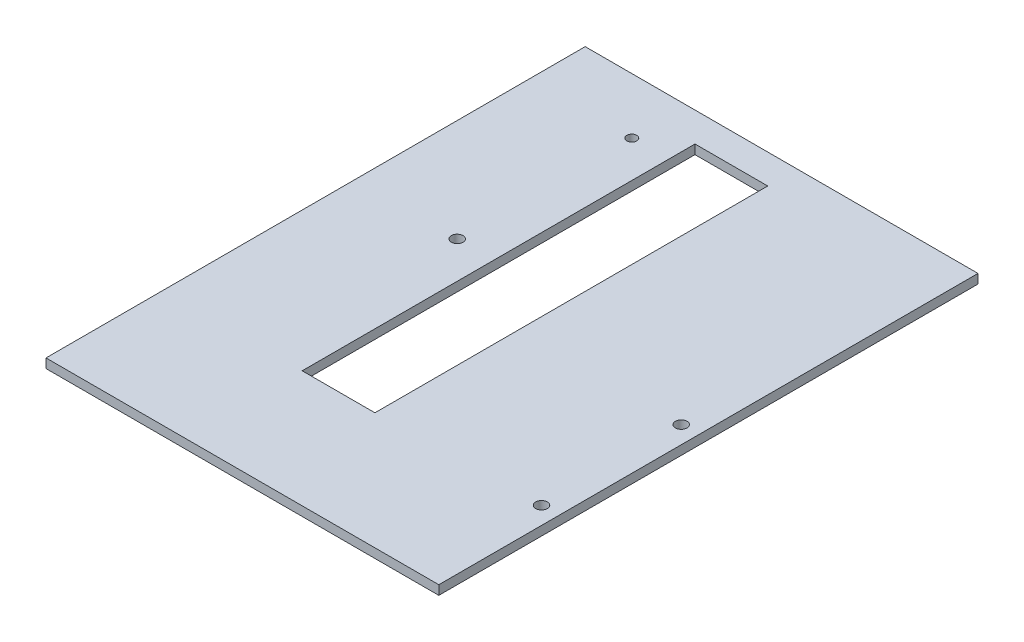
SolidWorks part; units mm, degrees
ref_plane "Front Plane" through (0, 0, 0) normal (0, 0, 1) x (1, 0, 0)
ref_plane "Top Plane" through (0, 0, 0) normal (0, 1, 0) x (1, 0, 0)
ref_plane "Right Plane" through (0, 0, 0) normal (1, 0, 0) x (0, 0, -1)
sketch "Sketch1" plane through (0, 0, 0) normal (0, 1, 0) x (1, 0, 0)
  line L0 (-19.4743, 15.0395) -> (5.5257, 15.0395) construction
  line L1 (67.6743, 92.6518) -> (67.6743, -92.6518)
  line L2 (67.6743, -92.6518) -> (-67.3257, -92.6518)
  line L3 (-67.3257, -92.6518) -> (-67.3257, -57.3482)
  line L4 (-6.9743, 75.2355) -> (-6.9743, -88.6335) construction
  line L5 (67.6743, 92.6518) -> (-67.3257, 92.6518)
  line L6 (-67.3257, -57.3482) -> (-67.3257, 92.6518)
  line L7 (-19.4743, 82.5395) -> (5.5257, 82.5395)
  line L8 (-19.4743, 82.5395) -> (-19.4743, -52.4605)
  line L9 (-19.4743, -52.4605) -> (5.5257, -52.4605)
  line L10 (5.5257, 82.5395) -> (5.5257, -52.4605)
  circle A0 centre (61.6743, -3.3482) radius 2
  circle A1 centre (61.6743, -51.3482) radius 2
  circle A2 centre (-32.0866, 13.4274) radius 2 construction
  circle A3 centre (-32.0866, 73.4274) radius 1.7 construction
  circle A4 centre (-32.0866, 13.4274) radius 2
  circle A5 centre (-32.0866, 73.4274) radius 1.7
  dimension "D2" = 4
  dimension "D3" = 4
  dimension "D1" = 25
  dimension "D4" = 48
  dimension "D5" = 6
  dimension "D6" = 135
  dimension "D7" = 135
  dimension "D9" = 185.3036
extrude "Boss-Extrude1" add sketch "Sketch1" along normal blind 3.175
